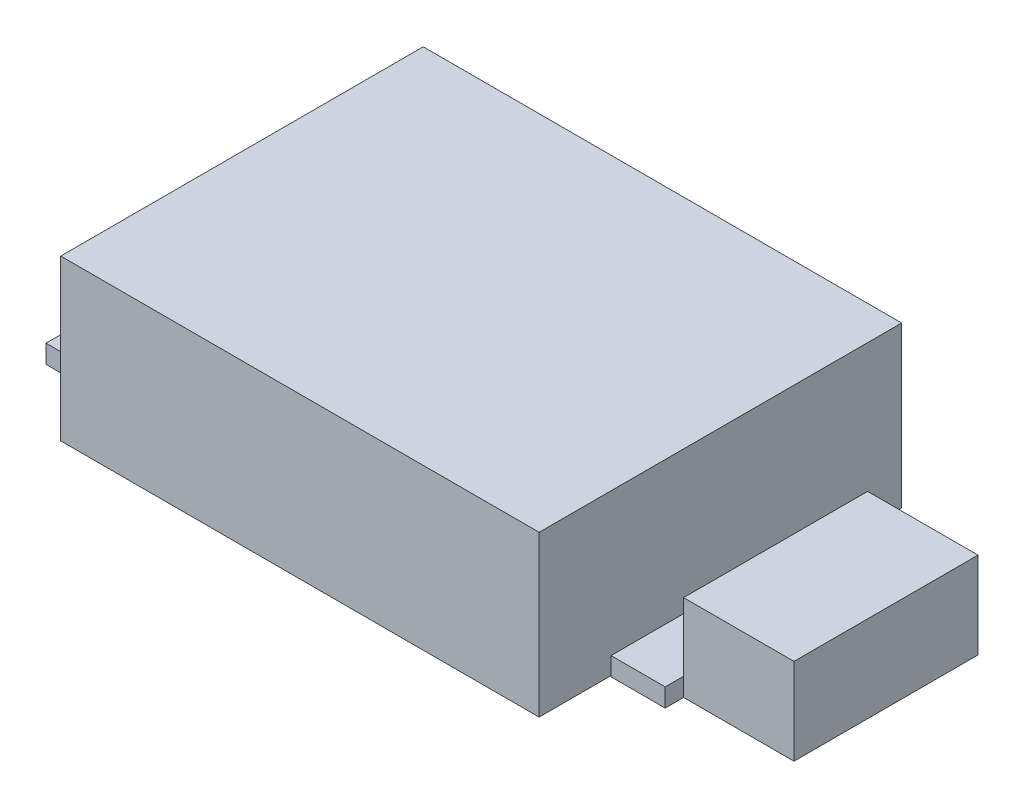
SolidWorks part; units mm, degrees
ref_plane "Спереди" through (0, 0, 0) normal (0, 0, 1) x (1, 0, 0)
ref_plane "Сверху" through (0, 0, 0) normal (0, 1, 0) x (1, 0, 0)
ref_plane "Справа" through (0, 0, 0) normal (1, 0, 0) x (0, 0, -1)
sketch "Эскиз1" plane through (0, 0, 0) normal (0, 1, 0) x (1, 0, 0)
  line L0 (13, 0) -> (-13, 0) construction
  line L1 (13, 9.85) -> (-13, 9.85)
  line L2 (13, 9.85) -> (13, -9.85)
  line L3 (13, -9.85) -> (-13, -9.85)
  line L4 (-13, 9.85) -> (-13, -9.85)
  line L5 (13, 9.85) -> (-13, -9.85) construction
  line L6 (13, -9.85) -> (-13, 9.85) construction
  line L7 (-13, 6.65) -> (-13, -6.65)
  line L8 (-13, -6.65) -> (-13, 6.65)
  line L9 (-13, -6.65) -> (-17, -6.65)
  line L10 (-13, 6.65) -> (-17, 6.65)
  line L11 (-17, -6.65) -> (-17, 6.65)
  line L12 (13, 5) -> (13, -5)
  line L13 (13, 5) -> (13, -5)
  line L14 (13, 5) -> (22, 5)
  line L15 (13, -5) -> (22, -5)
  line L16 (22, 5) -> (22, -5)
  line L17 (13, 0) -> (22, 0) construction
  line L18 (16, 6) -> (16, -6)
  line L19 (16, 6) -> (16, -6)
  line L20 (16, 6) -> (13.0573, 6)
  line L21 (16, -6) -> (13.0573, -6)
  line L22 (13.0573, 6) -> (13.0573, -6)
  point P0 (0, 0)
  point P11 (-13, 0)
  point P16 (13, 0)
  point P22 (16, 0)
  dimension "D1" = 26
  dimension "D2" = 19.7
  dimension "D3" = 13.3
  dimension "D4" = 10
  dimension "D5" = 39
  dimension "D6" = 3
  dimension "D7" = 4
  dimension "D8" = 12
  dimension "D9" = 9
  dimension "D10" = 6
extrude "Бобышка-Вытянуть1" add sketch "Эскиз1" along normal blind 1 contours L11 L9 L4 L10 | L20 L22 L14 L18 | L14 L22 L15 L18 | L15 L22 L21 L18 region at (-15, 0, 0) region at (14.5286, 0, -5.5) region at (14.5286, 0, 0) region at (14.5286, 0, 5.5)
extrude "Бобышка-Вытянуть2" add sketch "Эскиз1<4>" along normal blind 8.7 contours L1 L4 L3 L2 region at (0, 0, 0)
sketch "Эскиз1<4>" plane through (0, 0, 0) normal (0, 1, 0) x (1, 0, 0) same geometry as "Эскиз1"
extrude "Бобышка-Вытянуть3" add sketch "Эскиз1<5>" along normal blind 4.7 contours L14 L18 L15 L16 region at (19, 0, 0)
sketch "Эскиз1<5>" plane through (0, 0, 0) normal (0, 1, 0) x (1, 0, 0) same geometry as "Эскиз1"
